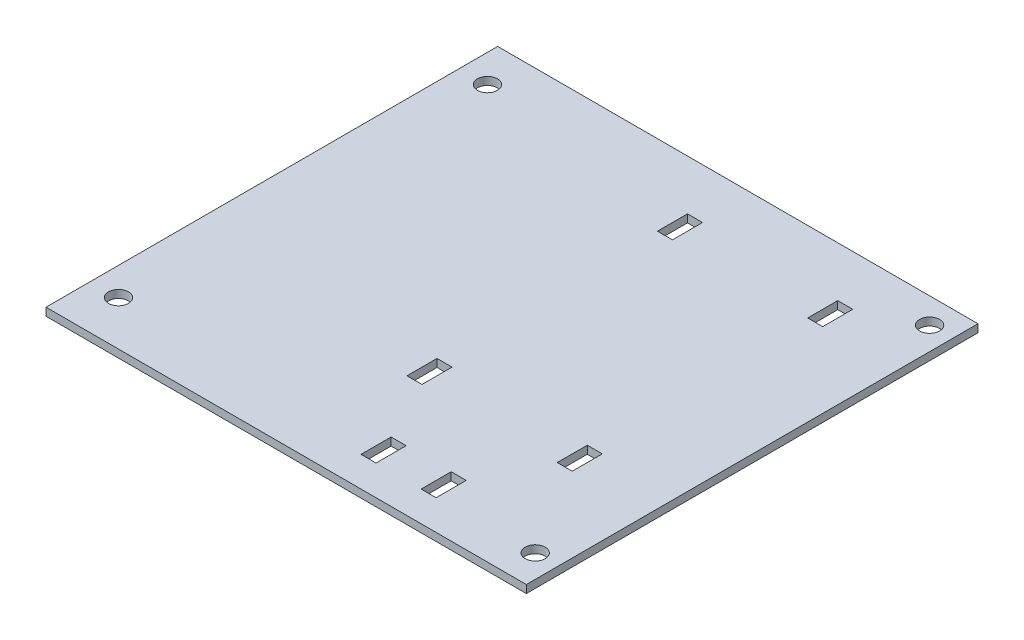
SolidWorks part; units mm, degrees
other "DetailItem3"
material "ABS"
ref_plane "Front Plane" through (0, 0, 0) normal (0, 0, 1) x (1, 0, 0)
ref_plane "Top Plane" through (0, 0, 0) normal (0, 1, 0) x (1, 0, 0)
ref_plane "Right Plane" through (0, 0, 0) normal (1, 0, 0) x (0, 0, -1)
sketch "Sketch1" plane through (0, 0, 0) normal (0, 1, 0) x (1, 0, 0)
  line L1 (-32.2441, 108.719) -> (64.6459, 108.719)
  line L2 (-32.2441, 108.719) -> (-32.2441, 18.549)
  line L3 (-32.2441, 18.549) -> (64.6459, 18.549)
  line L4 (64.6459, 108.719) -> (64.6459, 18.549)
  dimension "D1" = 96.89
  dimension "D2" = 90.17
extrude "PCB" add sketch "Sketch1" along normal blind 1.57
sketch "Sketch2" plane through (0, 1.57, 0) normal (0, 1, 0) x (1, 0, 0)
  line L0 (64.6459, 18.549) -> (64.6459, 108.719) construction
  line L1 (-32.2441, 18.549) -> (64.6459, 18.549) construction
  circle A0 centre (59.5659, 24.899) radius 2
  circle A1 centre (-26.1641, 27.439) radius 2
  circle A2 centre (-26.1641, 101.099) radius 2
  circle A3 centre (59.5659, 103.639) radius 2
  dimension "D3" = 4
  dimension "D6" = 4
  dimension "D11" = 4
  dimension "D12" = 4
  dimension "D1" = 5.08
  dimension "D2" = 6.35
  dimension "D4" = 90.81
  dimension "D5" = 8.89
  dimension "D7" = 90.81
  dimension "D8" = 5.08
  dimension "D9" = 85.09
  dimension "D10" = 82.55
extrude "M3 Mounting Holes" cut sketch "Sketch2" against normal blind 1.57
sketch "Sketch5" plane through (0, 1.57, 0) normal (0, 1, 0) x (1, 0, 0)
  line L0 (64.6459, 108.719) -> (-32.2441, 108.719) construction
  line L1 (-32.2441, 18.549) -> (-31.7441, 18.549)
  line L2 (-32.2441, 18.549) -> (-32.2441, 108.719)
  line L3 (-32.2441, 108.719) -> (-31.7441, 108.719)
  line L4 (-31.7441, 18.549) -> (-31.7441, 108.719)
  line L5 (-32.2441, 18.549) -> (64.6459, 18.549) construction
  line L6 (64.6459, 108.719) -> (64.1459, 108.719)
  line L7 (64.6459, 108.719) -> (64.6459, 18.549)
  line L8 (64.6459, 18.549) -> (64.1459, 18.549)
  line L9 (64.1459, 108.719) -> (64.1459, 18.549)
  dimension "D1" = 0.5
  dimension "D2" = 0.5
extrude "Cut-Extrude1" cut sketch "Sketch5" against normal through all
sketch "Sketch6" plane through (0, 1.57, 0) normal (0, 1, 0) x (1, 0, 0)
  line L1 (16.1459, 98.719) -> (19.1459, 98.719)
  line L2 (16.1459, 98.719) -> (16.1459, 92.719)
  line L3 (16.1459, 92.719) -> (19.1459, 92.719)
  line L4 (19.1459, 98.719) -> (19.1459, 92.719)
  line L5 (46.1459, 98.719) -> (49.1459, 98.719)
  line L6 (46.1459, 98.719) -> (46.1459, 92.719)
  line L7 (46.1459, 92.719) -> (49.1459, 92.719)
  line L8 (49.1459, 98.719) -> (49.1459, 92.719)
  line L9 (16.1459, 48.719) -> (19.1459, 48.719)
  line L10 (16.1459, 48.719) -> (16.1459, 42.719)
  line L11 (16.1459, 42.719) -> (19.1459, 42.719)
  line L12 (19.1459, 48.719) -> (19.1459, 42.719)
  line L13 (46.1459, 48.719) -> (49.1459, 48.719)
  line L14 (46.1459, 48.719) -> (46.1459, 42.719)
  line L15 (46.1459, 42.719) -> (49.1459, 42.719)
  line L16 (49.1459, 48.719) -> (49.1459, 42.719)
  line L17 (64.1459, 108.719) -> (-31.7441, 108.719) construction
  line L18 (64.1459, 108.719) -> (64.1459, 18.549) construction
  line L19 (-31.7441, 18.549) -> (64.1459, 18.549) construction
  line L20 (25.1459, 30.549) -> (28.1459, 30.549)
  line L21 (25.1459, 30.549) -> (25.1459, 24.549)
  line L22 (25.1459, 24.549) -> (28.1459, 24.549)
  line L23 (28.1459, 30.549) -> (28.1459, 24.549)
  line L24 (37.1459, 30.549) -> (40.1459, 30.549)
  line L25 (37.1459, 30.549) -> (37.1459, 24.549)
  line L26 (37.1459, 24.549) -> (40.1459, 24.549)
  line L27 (40.1459, 30.549) -> (40.1459, 24.549)
  dimension "D1" = 3
  dimension "D2" = 6
  dimension "D3" = 6
  dimension "D4" = 3
  dimension "D5" = 10
  dimension "D6" = 10
  dimension "D7" = 27
  dimension "D8" = 15
  dimension "D9" = 6
  dimension "D10" = 6
  dimension "D11" = 3
  dimension "D12" = 3
  dimension "D13" = 15
  dimension "D14" = 27
  dimension "D15" = 50
  dimension "D16" = 50
  dimension "D17" = 3
  dimension "D18" = 6
  dimension "D19" = 6
  dimension "D20" = 3
  dimension "D21" = 6
  dimension "D22" = 6
  dimension "D23" = 6
  dimension "D24" = 6
extrude "ZipTie Holds" cut sketch "Sketch6" against normal blind 10
